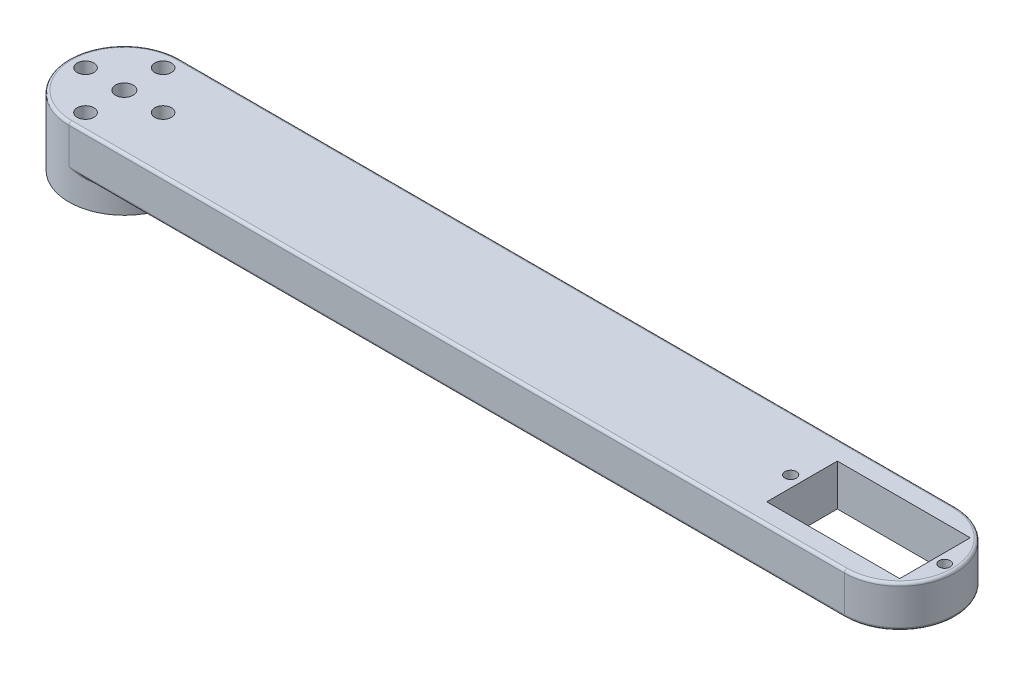
SolidWorks part; units mm, degrees
ref_plane "Front Plane" through (0, 0, 0) normal (0, 0, 1) x (1, 0, 0)
ref_plane "Top Plane" through (0, 0, 0) normal (0, 1, 0) x (1, 0, 0)
ref_plane "Right Plane" through (0, 0, 0) normal (1, 0, 0) x (0, 0, -1)
sketch "Sketch1" plane through (0, 0, 0) normal (0, 1, 0) x (1, 0, 0)
  line L0 (0, 0) -> (140, 0) construction
  line L2 (0, 10) -> (140, 10)
  line L3 (0, -10) -> (140, -10)
  line L4 (146.35, 6.375) -> (122.35, 6.375)
  line L5 (146.35, 6.375) -> (146.35, -6.375)
  line L6 (146.35, -6.375) -> (122.35, -6.375)
  line L7 (122.35, 6.375) -> (122.35, -6.375)
  arc A2 (0, 10) -> (0, -10) centre (0, 0) ccw
  arc A3 (140, -10) -> (140, 10) centre (140, 0) ccw
  circle A4 centre (0, 0) radius 1.6
  circle A11 centre (148.101, -0.0081) radius 1.001
  circle A12 centre (120.301, -0.0011) radius 1.0347
  circle A17 centre (7, 0) radius 1.51
  circle A18 centre (0, -7) radius 1.51
  circle A19 centre (-7, 0) radius 1.51
  circle A20 centre (0, 7) radius 1.51
  point P5 (70, 0)
  point P29 (0, 0)
  point P30 (0, 0)
  dimension "D1" = 140
  dimension "D4" = 27.8
  dimension "D5" = 7
  dimension "D2" = 24
  dimension "D3" = 12.75
  dimension "D7" = 3.625
  dimension "D8" = 3.625
  dimension "D6" = 4
extrude "Boss-Extrude1" add sketch "Sketch1" along normal blind 7.5
sketch "Sketch6" plane through (0, 0, 0) normal (0, -1, 0) x (1, 0, 0)
  circle A0 centre (0, 0) radius 10
sketch "Sketch7" plane through (0, 0, 0) normal (0, -1, 0) x (1, 0, 0)
  circle A0 centre (0, 0) radius 10
  circle A1 centre (0, 7) radius 1.51
  circle A2 centre (7, 0) radius 1.51
  circle A3 centre (0, -7) radius 1.51
  circle A4 centre (-7, 0) radius 1.51
  circle A5 centre (0, 0) radius 1.6
  point P13 (0, 0)
  dimension "D1" = 4
extrude "Boss-Extrude4" add sketch "Sketch7" along normal blind 5
fillet "Fillet2" radius 0.5 8 edges at (150, 0, 0) (70, 0, -10) (10, 0, 0) (70, 0, 10) (150, 7.5, 0) (70, 7.5, -10) (-10, 7.5, 0) (70, 7.5, 10)
